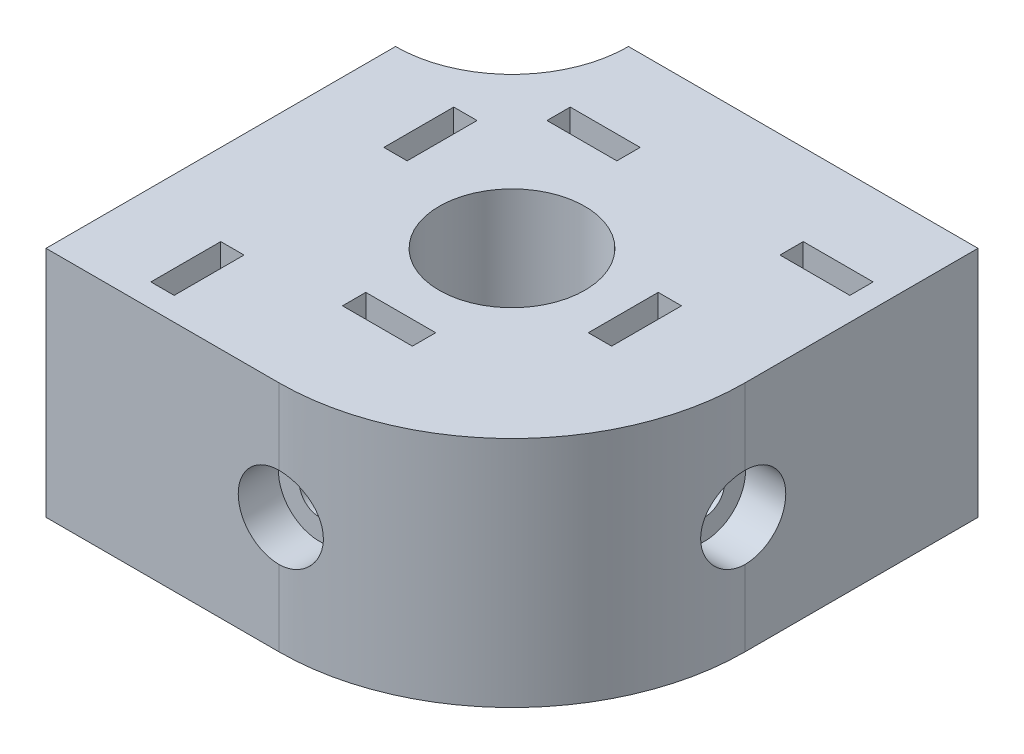
SolidWorks part; units mm, degrees
ref_plane "Front Plane" through (0, 0, 0) normal (0, 0, 1) x (1, 0, 0)
ref_plane "Top Plane" through (0, 0, 0) normal (0, 1, 0) x (1, 0, 0)
ref_plane "Right Plane" through (0, 0, 0) normal (1, 0, 0) x (0, 0, -1)
sketch "Sketch1" plane through (0, 0, 0) normal (0, 1, 0) x (1, 0, 0)
  line L1 (-20, -20) -> (20, -20)
  line L2 (-20, -20) -> (-20, 20)
  line L3 (-20, 20) -> (20, 20)
  line L4 (20, -20) -> (20, 20)
  line L5 (-20, -20) -> (20, 20) construction
  line L6 (-20, 20) -> (20, -20) construction
  circle A0 centre (0, 0) radius 6.25
  point P0 (0, 0)
  dimension "D2" = 12.5
  dimension "D1" = 40
extrude "Boss-Extrude1" add sketch "Sketch1" along normal blind 20
sketch "Sketch2" plane through (-20, 0, 0) normal (-1, 0, 0) x (0, 0, 1)
  line L0 (-5, 15) -> (0, 5) construction
  line L1 (0, 5) -> (15, 15) construction
  line L2 (15, 15) -> (-5, 15) construction
  line L3 (-20, 20) -> (20, 20) construction
  line L4 (-20, 0) -> (20, 0) construction
  line L5 (20, 20) -> (20, 0) construction
  line L6 (-20, 20) -> (-20, 0) construction
  line L7 (0, -11) -> (0, 11) construction
  circle A0 centre (-5, 15) radius 1.7
  circle A1 centre (15, 15) radius 1.7
  circle A2 centre (0, 5) radius 1.7
  dimension "D5" = 3.4
  dimension "D1" = 5
  dimension "D2" = 5
  dimension "D3" = 5
  dimension "D4" = 15
extrude "Cut-Extrude1" cut sketch "Sketch2" against normal blind 11
sketch "Sketch3" plane through (-20, 0, 0) normal (-1, 0, 0) x (0, 0, 1)
  line L1 (-8, 12) -> (-2, 12)
  line L2 (-8, 12) -> (-8, 18)
  line L3 (-8, 18) -> (-2, 18) construction
  line L4 (-2, 12) -> (-2, 18)
  line L5 (-8, 12) -> (-2, 18) construction
  line L6 (-8, 18) -> (-2, 12) construction
  line L7 (12, 12) -> (18, 12)
  line L8 (12, 12) -> (12, 18)
  line L9 (12, 18) -> (18, 18) construction
  line L10 (18, 12) -> (18, 18)
  line L11 (12, 12) -> (18, 18) construction
  line L12 (12, 18) -> (18, 12) construction
  line L13 (-3, 8) -> (3, 8)
  line L14 (-3, 8) -> (-3, 2)
  line L15 (-3, 2) -> (3, 2) construction
  line L16 (3, 8) -> (3, 2)
  line L17 (-3, 8) -> (3, 2) construction
  line L18 (-3, 2) -> (3, 8) construction
  line L20 (-8, 18) -> (-8, 20)
  line L21 (-20, 20) -> (20, 20) construction
  line L22 (-8, 20) -> (-2, 20)
  line L23 (-2, 20) -> (-2, 18)
  line L24 (12, 18) -> (12, 20)
  line L25 (12, 20) -> (18, 20)
  line L26 (18, 20) -> (18, 18)
  line L27 (-3, 2) -> (-3, 0)
  line L28 (-20, 0) -> (20, 0) construction
  line L29 (-3, 0) -> (3, 0)
  line L30 (3, 0) -> (3, 2)
  point P0 (-5, 15)
  point P6 (15, 15)
  point P12 (0, 5)
  dimension "D1" = 6
  dimension "D2" = 6
extrude "Cut-Extrude2" cut sketch "Sketch3" against normal blind 2 from offset 7 offset against normal yes
sketch "Sketch4" plane through (0, 0, 20) normal (0, 0, 1) x (1, 0, 0)
  line L0 (0, 0) -> (0, 20) construction
  line L1 (-20, 20) -> (20, 20) construction
  circle A0 centre (0, 10) radius 1.7
  dimension "D1" = 3.4
extrude "Cut-Extrude3" cut sketch "Sketch4" against normal up to next
sketch "Sketch5" plane through (0, 0, 20) normal (0, 0, 1) x (1, 0, 0)
  line L0 (-3, 13) -> (-3, 20)
  line L1 (-3, 7) -> (3, 7)
  line L2 (-3, 7) -> (-3, 13)
  line L3 (-3, 13) -> (3, 13) construction
  line L4 (3, 7) -> (3, 13)
  line L5 (-3, 7) -> (3, 13) construction
  line L6 (-3, 13) -> (3, 7) construction
  line L7 (-20, 20) -> (20, 20) construction
  line L8 (-3, 20) -> (3, 20)
  line L9 (3, 20) -> (3, 13)
  point P0 (0, 10)
  dimension "D1" = 6
extrude "Cut-Extrude4" cut sketch "Sketch5" against normal blind 2 from offset 8.45 offset against normal yes
sketch "Sketch6" plane through (0, 0, 20) normal (0, 0, 1) x (1, 0, 0)
  circle A0 centre (0, 10) radius 3.5
  dimension "D1" = 7
extrude "Cut-Extrude5" cut sketch "Sketch6" against normal blind 3.45
ref_plane "Plane1" through (0, 0, 0) normal (-0.7071, 0, 0.7071) x (0.7071, 0, 0.7071)
mirror "Mirror1" about plane through (0, 0, 0) normal (-0.7071, 0, 0.7071) of "Cut-Extrude5", "Cut-Extrude4", "Cut-Extrude3", "Cut-Extrude2", "Cut-Extrude1"
fillet "Fillet1" radius 20 1 edges at (20, 10, 20)
sketch "Sketch7" plane through (0, 20, 0) normal (0, 1, 0) x (1, 0, 0)
  line L0 (20, 20) -> (-20, 20) construction
  line L1 (-20, 20) -> (-20, -20) construction
  line L2 (-20, 10) -> (-20, 20)
  line L3 (-20, 20) -> (-10, 20)
  arc A0 (-10, 20) -> (-20, 10) centre (-20, 20) cw
  dimension "D1" = 10
extrude "Cut-Extrude6" cut sketch "Sketch7" against normal through all
equation "\"M3_d\"= 3.4"
equation "\"D5@Sketch2\"= \"M3_d\""
equation "\"M3_nut_s\" = 6"
equation "\"M3_nut_m\" = 2"
equation "\"D1@Sketch3\"=\"M3_nut_s\""
equation "\"D2@Sketch3\"=\"M3_nut_s\" "
equation "\"D1@Cut-Extrude2\"=\"M3_nut_m\""
equation "\"D1@Sketch4\"=\"M3_d\""
equation "\"D1@Sketch5\"=\"M3_nut_s\""
equation "\"D1@Cut-Extrude4\"=\"M3_nut_m\""
